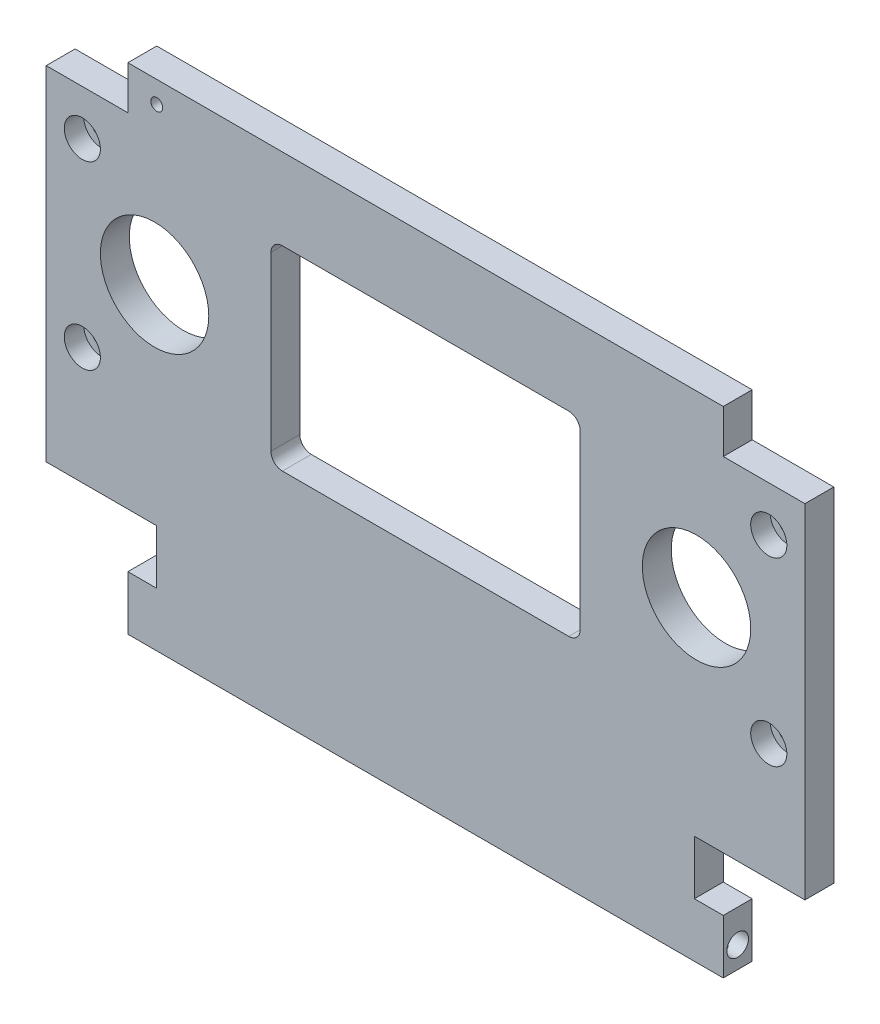
SolidWorks part; units mm, degrees
ref_plane "前视基准面" through (0, 0, 0) normal (0, 0, 1) x (1, 0, 0)
ref_plane "上视基准面" through (0, 0, 0) normal (0, 1, 0) x (1, 0, 0)
ref_plane "右视基准面" through (0, 0, 0) normal (1, 0, 0) x (0, 0, -1)
sketch "草图1" plane through (0, 0, 0) normal (0, 0, 1) x (1, 0, 0)
  line L1 (0, 0) -> (210, 0)
  line L2 (0, 0) -> (0, 75)
  line L3 (0, 75) -> (210, 75)
  line L4 (210, 0) -> (210, 75)
  dimension "D1" = 210
  dimension "D2" = 75
extrude "凸台-拉伸1" add sketch "草图1" along normal blind 8
sketch "草图2" plane through (0, 0, 8) normal (0, 0, 1) x (1, 0, 0)
  line L0 (210, 37.5) -> (0, 37.5) construction
  line L1 (210, 0) -> (210, 75) construction
  line L2 (0, 75) -> (0, 0) construction
  line L3 (0, 37.5) -> (105, 37.5) construction
  line L4 (105, 37.5) -> (105, -2.643) construction
  line L6 (144.62, 64.5) -> (65.38, 64.5)
  line L7 (147.8, 61.32) -> (147.8, 13.68)
  line L8 (144.62, 10.5) -> (65.38, 10.5)
  line L9 (62.2, 61.32) -> (62.2, 13.68)
  arc A0 (65.38, 10.5) -> (62.2, 13.68) centre (65.38, 13.68) cw
  arc A1 (62.2, 61.32) -> (65.38, 64.5) centre (65.38, 61.32) cw
  arc A2 (144.62, 10.5) -> (147.8, 13.68) centre (144.62, 13.68) ccw
  arc A3 (144.62, 64.5) -> (147.8, 61.32) centre (144.62, 61.32) cw
  point P16 (62.2, 64.5)
  point P19 (147.8, 10.5)
  point P22 (147.8, 64.5)
  dimension "D3" = 3.18
  dimension "D1" = 54
  dimension "D2" = 85.6
extrude "切除-拉伸1" cut sketch "草图2" against normal through all
hole_wizard "M5 六角凹头螺钉的柱形沉头孔1" positions "草图3" profile "草图4" counterbore size "M5" standard "ISO"
sketch "草图3" plane through (0, 0, 8) normal (0, 0, 1) x (1, 0, 0)
  line L0 (0, 37.5) -> (210, 37.5) construction
  line L1 (0, 75) -> (0, 0) construction
  line L2 (210, 0) -> (210, 75) construction
  line L3 (210, 37.5) -> (105, 37.5) construction
  line L4 (105, 37.5) -> (105, -47.7536) construction
  point P0 (10, 62.5)
  point P4 (10, 12.5)
  point P18 (200, 62.5)
  point P19 (200, 12.5)
  dimension "D1" = 50
  dimension "D2" = 10
sketch "草图4" plane through (10, 62.5, 8) normal (1, 0, 0) x (0, -1, 0)
  line L0 (0, 0) -> (0, 11.7524)
  line L1 (0, 11.7524) -> (2.75, 10.1)
  line L2 (2.75, 10.1) -> (2.75, 5.4)
  line L3 (2.75, 5.4) -> (5, 5.4)
  line L4 (5, 5.4) -> (5, 0)
  line L5 (5, 0) -> (0, 0)
  line L10 (0, 11.7524) -> (-2.75, 10.1) construction
  line L11 (0, -6.35) -> (0, 107.95) construction
  dimension "孔直径" = 5.5
  dimension "孔深度" = 10.1
  dimension "柱形沉头孔直径" = 10
  dimension "柱形沉头孔深度" = 5.4
  dimension "导头角度" = 118
sketch "草图5" plane through (0, 0, 8) normal (0, 0, 1) x (1, 0, 0)
  line L0 (0, 37.5) -> (210, 37.5) construction
  line L1 (0, 75) -> (0, 0) construction
  line L2 (210, 0) -> (210, 75) construction
  line L3 (210, 37.5) -> (105, 37.5) construction
  line L4 (105, 37.5) -> (105, 124.5038) construction
  circle A0 centre (30, 37.5) radius 15
  circle A1 centre (180, 37.5) radius 15
  dimension "D1" = 30
  dimension "D2" = 30
extrude "切除-拉伸2" cut sketch "草图5" against normal blind 13
sketch "草图6" plane through (0, 0, 0) normal (0, -1, 0) x (1, 0, 0)
  line L1 (0, 8) -> (210, 8)
  line L2 (0, 8) -> (0, 0)
  line L3 (0, 0) -> (210, 0)
  line L4 (210, 8) -> (210, 0)
extrude "凸台-拉伸2" add sketch "草图6" along normal blind 50
sketch "草图7" plane through (0, 0, 8) normal (0, 0, 1) x (1, 0, 0)
  line L0 (105, -50) -> (105, 47.0647) construction
  line L1 (0, -50) -> (22.6, -50)
  line L2 (0, -50) -> (0, -20)
  line L3 (0, -20) -> (22.6, -20)
  line L4 (22.6, -50) -> (22.6, -20)
  line L5 (210, -50) -> (0, -50) construction
  line L6 (210, -50) -> (210, -20)
  line L7 (210, -50) -> (187.4, -50)
  line L8 (187.4, -50) -> (187.4, -20)
  line L9 (210, -20) -> (187.4, -20)
  dimension "D1" = 30
  dimension "D2" = 22.6
extrude "切除-拉伸3" cut sketch "草图7" against normal blind 20
sketch "草图9" plane through (22.6, 0, 0) normal (-1, 0, 0) x (0, 0, 1)
  circle A0 centre (3.996, -44.028) radius 3
  dimension "D1" = 6
extrude "切除-拉伸5" cut sketch "草图9" against normal blind 8
ref_plane "基准面1" through (105, 0, 0) normal (-1, 0, 0) x (0, 0, 1)
mirror "镜向1" about plane through (105, 0, 0) normal (-1, 0, 0) of "切除-拉伸5"
ref_plane "基准面2" through (0, 27.5, 0) normal (0, 1, 0) x (1, 0, 0)
sketch "草图12" plane through (0, 75, 0) normal (0, 1, 0) x (1, 0, 0)
  line L0 (105, -8) -> (105, 0) construction
  line L1 (210, -8) -> (0, -8) construction
  line L2 (210, 0) -> (0, 0) construction
  line L4 (187.4, -8) -> (22.6, -8)
  line L5 (187.4, -8) -> (187.4, 0)
  line L6 (187.4, 0) -> (22.6, 0)
  line L7 (22.6, -8) -> (22.6, 0)
  dimension "D1" = 164.8
extrude "凸台-拉伸3" add sketch "草图12" along normal blind 12
sketch "草图13" plane through (0, 0, 8) normal (0, 0, 1) x (1, 0, 0)
  line L0 (105, -50) -> (105, 27.2823) construction
  line L1 (22.6, -20) -> (30.6, -20)
  line L2 (22.6, -20) -> (22.6, -35)
  line L3 (22.6, -35) -> (30.6, -35)
  line L4 (30.6, -20) -> (30.6, -35)
  line L5 (187.4, -50) -> (22.6, -50) construction
  line L6 (187.4, -20) -> (187.4, -35)
  line L7 (187.4, -35) -> (179.4, -35)
  line L8 (179.4, -20) -> (179.4, -35)
  line L9 (187.4, -20) -> (179.4, -20)
  dimension "D1" = 8
  dimension "D2" = 15
extrude "切除-拉伸6" cut sketch "草图13" against normal through all
hole_wizard "M4 螺纹孔1" positions "草图14" profile "草图15" tap size "M4" standard "ISO"
sketch "草图14" plane through (0, -50, 0) normal (0, -1, 0) x (-1, 0, 0)
  line L3 (-22.6, -4) -> (-187.4, -4) construction
  line L4 (-22.6, 0) -> (-22.6, -8) construction
  line L5 (-187.4, -8) -> (-187.4, 0) construction
  line L6 (-187.4, -4) -> (-105, -4) construction
  line L7 (-105, -4) -> (-105, -29.6967) construction
  point P0 (-27.6, -4.0022)
  point P20 (-182.4, -4.0022)
  dimension "D1" = 5
sketch "草图15" plane through (27.6, -50, 4.0022) normal (1, 0, 0) x (0, 0, -1)
  line L0 (0, 0) -> (0, 5.9914)
  line L1 (0, 5.9914) -> (1.65, 5)
  line L2 (1.65, 5) -> (1.65, 0)
  line L5 (1.65, 0) -> (0, 0)
  line L10 (0, 5.9914) -> (-1.65, 5) construction
  line L11 (0, -6.35) -> (0, 107.95) construction
  dimension "螺纹孔钻头直径" = 3.3
  dimension "螺纹孔钻头深度" = 5
  dimension "导头角度" = 118
cosmetic thread "孔螺蚊线1" parameters "D1"=3.4706, "D2"=4
cosmetic thread "孔螺蚊线2" parameters "D1"=3.4706, "D2"=4
hole_wizard "M4 螺纹孔2" positions "草图16" profile "草图17" tap size "M4" standard "ISO"
sketch "草图16" plane through (0, 0, 0) normal (0, 0, -1) x (-1, 0, 0)
  line L0 (-22.6, 87) -> (-22.6, 75) construction
  line L1 (-187.4, 87) -> (-22.6, 87) construction
  point P0 (-30.6, 81)
  point P3 (0, 0)
  dimension "D1" = 8
  dimension "D2" = 6
sketch "草图17" plane through (30.6, 81, 0) normal (1, 0, 0) x (0, 1, 0)
  line L0 (0, 0) -> (0, 11.0914)
  line L1 (0, 11.0914) -> (1.65, 10.1)
  line L2 (1.65, 10.1) -> (1.65, 0)
  line L5 (1.65, 0) -> (0, 0)
  line L10 (0, 11.0914) -> (-1.65, 10.1) construction
  line L11 (0, -6.35) -> (0, 107.95) construction
  dimension "螺纹孔钻头直径" = 3.3
  dimension "螺纹孔钻头深度" = 10.1
  dimension "导头角度" = 118
cosmetic thread "孔螺蚊线3" parameters "D1"=8, "D2"=4
